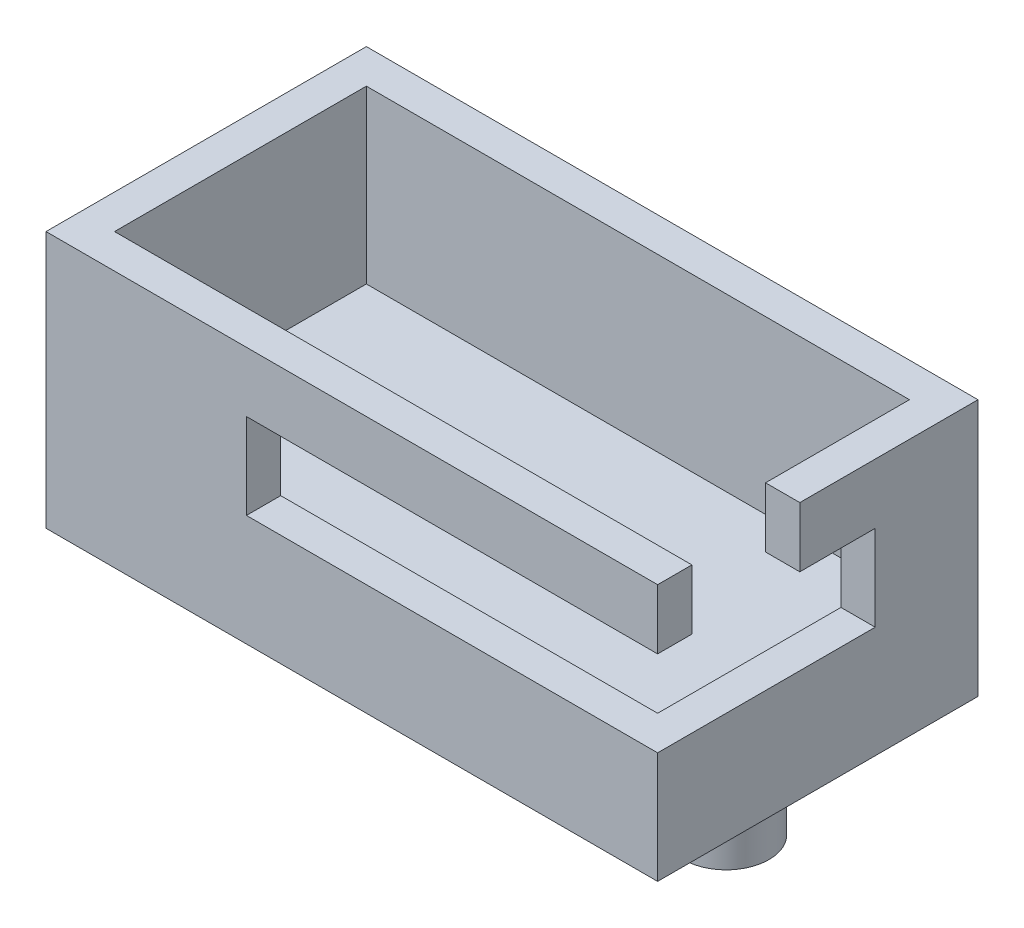
SolidWorks part; units mm, degrees
ref_plane "Front Plane" through (0, 0, 0) normal (0, 0, 1) x (1, 0, 0)
ref_plane "Top Plane" through (0, 0, 0) normal (0, 1, 0) x (1, 0, 0)
ref_plane "Right Plane" through (0, 0, 0) normal (1, 0, 0) x (0, 0, -1)
sketch "Sketch1" plane through (0, 0, 0) normal (0, 1, 0) x (1, 0, 0)
  line L0 (-2, -2) -> (-2, 16.7)
  line L1 (0, 0) -> (31.7, 0)
  line L2 (0, 0) -> (0, 14.7)
  line L3 (0, 14.7) -> (31.7, 14.7)
  line L4 (31.7, 0) -> (31.7, 14.7)
  line L5 (-2, 16.7) -> (33.7, 16.7)
  line L6 (33.7, -2) -> (33.7, 16.7)
  line L7 (-2, -2) -> (33.7, -2)
  dimension "D1" = 14.7
  dimension "D2" = 31.7
  dimension "D3" = 2
extrude "Boss-Extrude1" add sketch "Sketch1" along normal blind 10
extrude "Boss-Extrude2" add sketch "Sketch1<2>" against normal blind 5 contours L0 L7 L6 L5 L4 L1 L2 L3 | L1 L4 L3 L2 region at (-1.597, 0, -7.35) region at (15.85, 0, -7.35)
sketch "Sketch1<2>" plane through (0, 0, 0) normal (0, 1, 0) x (1, 0, 0) same geometry as "Sketch1"
sketch "Sketch2" plane through (0, 0, 2) normal (0, 0, 1) x (1, 0, 0)
  line L0 (33.7, 10) -> (33.7, -5) construction
  line L1 (9.7, 6.5) -> (33.7, 6.5)
  line L2 (9.7, 6.5) -> (9.7, 1.5)
  line L3 (9.7, 1.5) -> (33.7, 1.5)
  line L4 (33.7, 6.5) -> (33.7, 1.5)
  line L5 (-2, -5) -> (33.7, -5) construction
  dimension "D1" = 24
  dimension "D2" = 5
  dimension "D3" = 6.5
extrude "Cut-Extrude1" cut sketch "Sketch2" against normal offset from surface (12.7 mm away) 6 up to face at (15.85, 2.5, -16.7)
sketch "Sketch3" plane through (33.7, 0, 0) normal (1, 0, 0) x (0, 0, -1)
  line L0 (-2, 10) -> (16.7, 10) construction
  line L1 (0, 6.5) -> (6.3, 6.5)
  line L2 (0, 6.5) -> (0, 10)
  line L3 (0, 10) -> (6.3, 10)
  line L4 (6.3, 6.5) -> (6.3, 10)
  dimension "D1" = 6.3
extrude "Cut-Extrude2" cut sketch "Sketch3" against normal up to surface (2 mm away) up to face at (31.7, 4.5, -6.35)
sketch "Sketch4" plane through (0, -5, 0) normal (0, -1, 0) x (1, 0, 0)
  line L0 (15.85, 2) -> (15.85, -16.7) construction
  line L1 (-2, 2) -> (33.7, 2) construction
  line L2 (-2, -16.7) -> (33.7, -16.7) construction
  line L3 (3.35, -7.35) -> (15.85, -7.35) construction
  circle A0 centre (3.35, -7.35) radius 2.5
  circle A1 centre (28.35, -7.35) radius 2.5
  dimension "D1" = 5
  dimension "D2" = 12.5
extrude "Boss-Extrude3" add sketch "Sketch4" along normal blind 5
fillet "Fillet1" radius 0.4 2 edges at (28.35, -5, -4.85) (3.35, -5, -4.85)
